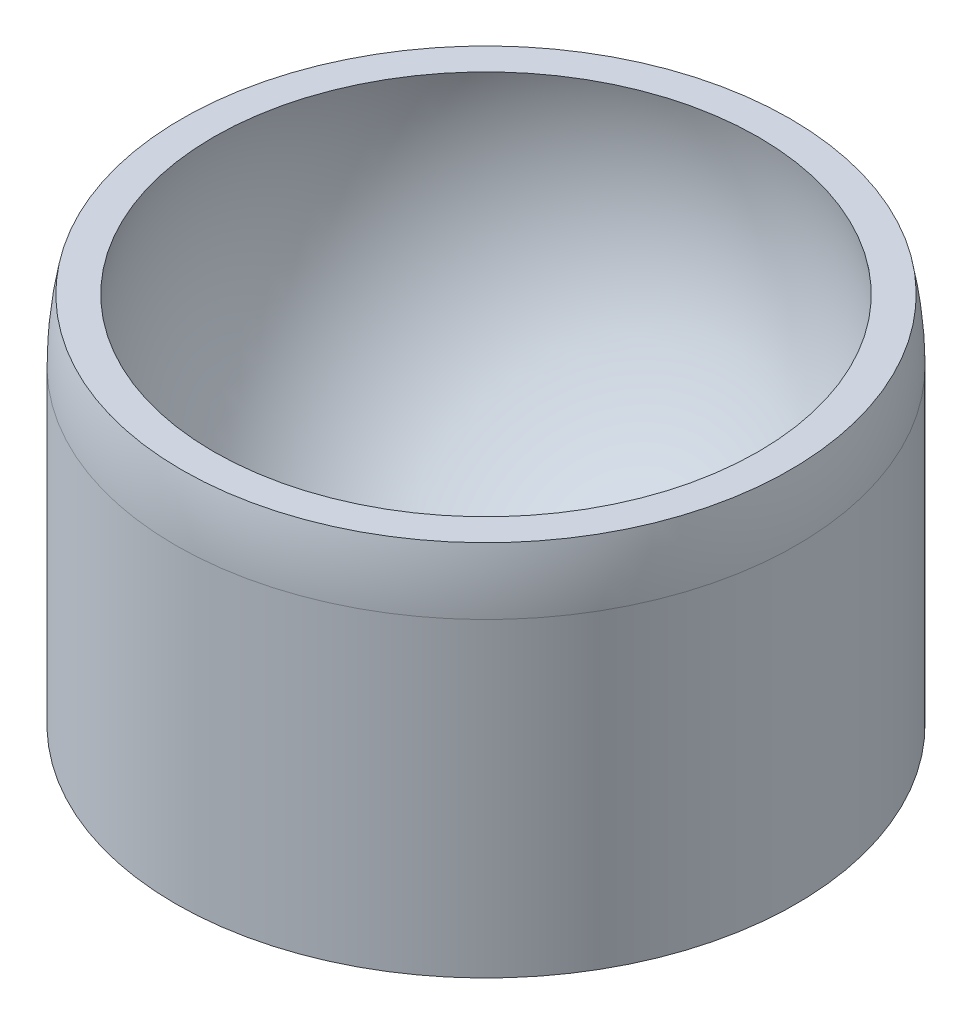
SolidWorks part; units mm, degrees
ref_plane "Front Plane" through (0, 0, 0) normal (0, 0, 1) x (1, 0, 0)
ref_plane "Top Plane" through (0, 0, 0) normal (0, 1, 0) x (1, 0, 0)
ref_plane "Right Plane" through (0, 0, 0) normal (1, 0, 0) x (0, 0, -1)
sketch "Sketch2" plane through (0, 0, 0) normal (0, 0, 1) x (1, 0, 0)
  line L0 (0, -10) -> (0, 10)
  line L1 (11, 0) -> (-11, 0) construction
  arc A0 (0, 10) -> (0, -10) centre (0, 0) cw
  dimension "D1" = 10
revolve "Revolve1" add sketch "Sketch2" angle 360 about L0
sketch "Sketch3" plane through (0, 0, 0) normal (1, 0, 0) x (0, 0, -1)
  line L0 (-10, 2) -> (10, 2)
  line L1 (-10, 2) -> (-10, 12)
  line L2 (10, 2) -> (10, 12)
  line L3 (-10, 12) -> (10, 12)
  line L4 (-10, 2) -> (10, 12) construction
  line L5 (10, 2) -> (-10, 12) construction
  point P1 (0, 7)
  dimension "D1" = 20
  dimension "D3" = 10
  dimension "D4" = 2
extrude "Cut-Extrude1" cut sketch "Sketch3" against normal blind 20 and the other way blind 20
shell "Shell1" thickness 1 removed face at (0, 2, 9.798)
ref_plane "Plane1" through (0, -10, 0) normal (0, 1, 0) x (1, 0, 0)
sketch "Sketch5" plane through (0, -10, 0) normal (0, 1, 0) x (1, 0, 0)
  circle A0 centre (0, 0) radius 10
  dimension "D1" = 20
extrude "Boss-Extrude1" add sketch "Sketch5" along normal up to body
equation "\"R1\"= 20mm"
equation "\"D1@Sketch2\"=\"R1\"/2"
equation "\"D1@Sketch3\"=\"R1\""
equation "\"D3@Sketch3\"=\"R1\"/2"
equation "\"D1@Cut-Extrude1\"=\"R1\""
equation "\"D2@Cut-Extrude1\"=\"R1\""
equation "\"R2\"= 18mm"
equation "\"D1@Sketch5\"=\"R1\""
